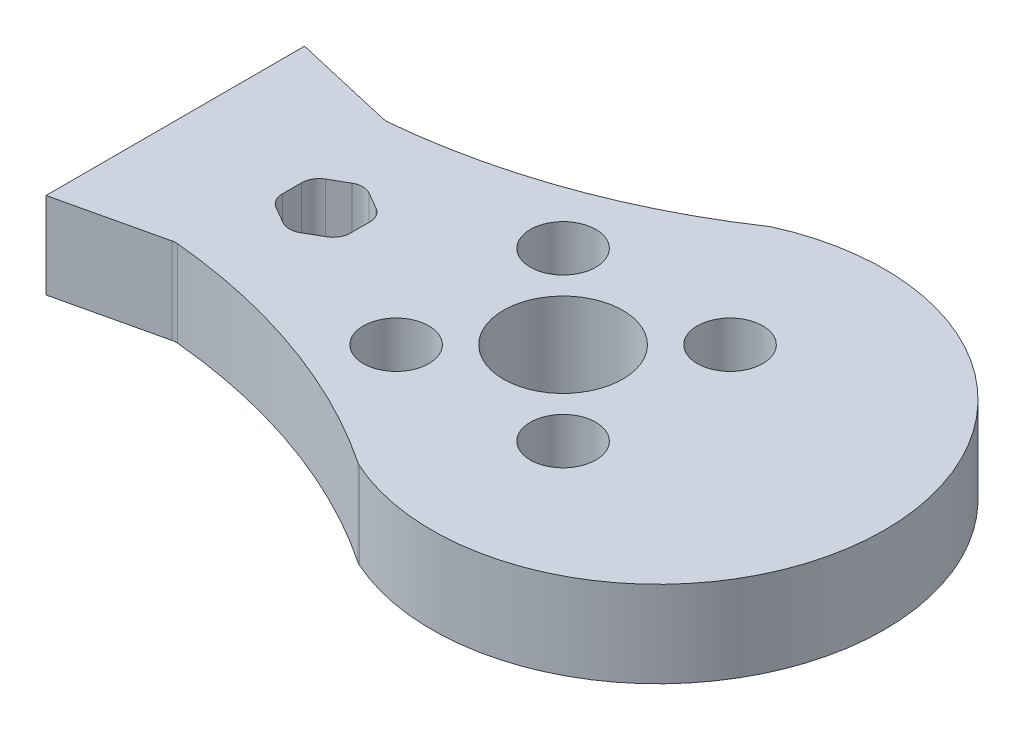
SolidWorks part; units mm, degrees
material "AISI 1020 Steel, Cold Rolled"
ref_plane "Front Plane" through (0, 0, 0) normal (0, 0, 1) x (1, 0, 0)
ref_plane "Top Plane" through (0, 0, 0) normal (0, 1, 0) x (1, 0, 0)
ref_plane "Right Plane" through (0, 0, 0) normal (1, 0, 0) x (0, 0, -1)
other "Center of Mass"
other "Bounding Box"
ref_plane "Default Plane" through (0, 2.286, 19.05) normal (0, -1, 0) x (-1, 0, 0)
sketch "Sketch1" plane through (0, 0, 0) normal (0, 1, 0) x (1, 0, 0)
  line L0 (0, 0) -> (27.8621, 0) construction
  line L1 (-12.303, 12.303) -> (12.303, 12.303) construction
  line L2 (-12.303, 12.303) -> (-12.303, -12.303) construction
  line L3 (-12.303, -12.303) -> (12.303, -12.303) construction
  line L4 (12.303, 12.303) -> (12.303, -12.303) construction
  line L5 (-12.303, 12.303) -> (12.303, -12.303) construction
  line L6 (-12.303, -12.303) -> (12.303, 12.303) construction
  line L7 (-57.15, 19.05) -> (-57.15, -19.05)
  line L8 (-57.15, -19.05) -> (-41.6819, -15.4789)
  line L9 (-39.9415, -2.8963) -> (-34.925, -5.7926)
  line L10 (-34.925, -5.7926) -> (-29.9085, -2.8963)
  line L11 (-29.9085, -2.8963) -> (-29.9085, 2.8963)
  line L12 (-29.9085, 2.8963) -> (-34.925, 5.7926)
  line L13 (-34.925, 5.7926) -> (-39.9415, 2.8963)
  line L14 (-39.9415, 2.8963) -> (-39.9415, -2.8963)
  line L15 (-57.15, 19.05) -> (-41.6819, 15.4789)
  circle A0 centre (0, 0) radius 8.7948
  circle A1 centre (-12.303, 12.303) radius 4.826
  circle A2 centre (12.303, 12.303) radius 4.826
  circle A3 centre (12.303, -12.303) radius 4.826
  circle A4 centre (-12.303, -12.303) radius 4.826
  arc A5 (0.2051, -30.3458) -> (0.2051, 30.3458) centre (14.0081, 0) ccw
  arc A8 (-41.6819, 15.4789) -> (0.2051, 30.3458) centre (-49.53, 104.0318) ccw
  arc A9 (0.2051, -30.3458) -> (-41.6819, -15.4789) centre (-49.53, -104.0318) ccw
  arc A10 (-19.3294, 0) -> (0.2051, -30.3458) centre (14.0081, 0) ccw construction
  circle A11 centre (-34.925, 0) radius 5.0165 construction
  arc A12 (-17.1157, 11.9456) -> (-19.3294, 0) centre (14.0081, 0) ccw construction
  arc A13 (-15.1145, 16.2254) -> (-17.1157, 11.9456) centre (14.0081, 0) ccw construction
  arc A14 (0.2051, 30.3458) -> (-15.1145, 16.2254) centre (14.0081, 0) ccw construction
  arc A15 (-57.15, 15.459) -> (-41.6819, 15.4789) centre (-49.53, 104.0318) ccw construction
  arc A16 (0.2051, 30.3458) -> (-57.15, 15.459) centre (-49.53, 104.0318) ccw construction
  arc A17 (-57.15, -15.459) -> (0.2051, -30.3458) centre (-49.53, -104.0318) ccw construction
  arc A18 (-41.6819, -15.4789) -> (-57.15, -15.459) centre (-49.53, -104.0318) ccw construction
  point P15 (-57.15, 0)
  point P33 (-49.8385, 104.0039)
  point P36 (-50.5698, -101.7291)
  point P37 (-54.0977, -101.4285)
  point P38 (0, 0)
  dimension "D1" = 17.5895
  dimension "D2" = 9.652
  dimension "D4" = 66.675
  dimension "D8" = 77
  dimension "D9" = 10.033
  dimension "D14" = 177.8
  dimension "D3" = 17.399
  dimension "D5" = 38.1
  dimension "D6" = 57.15
  dimension "D7" = 14.0081
  dimension "D10" = 34.925
  dimension "D11" = 47.3456
  dimension "D12" = 77
  dimension "D13" = 15.875
  dimension "D15" = 7.62
extrude "Boss-Extrude1" add sketch "Sketch1" along normal blind 12.7 contours A5 L7 A4 A3 A2 A1 A0 region at (-49.6948, 0, -16.0567)
fillet "Fillet1" radius 2.54 10 edges at (-39.9415, 6.35, 2.8963) (-34.925, 6.35, 5.7926) (-29.9085, 6.35, 2.8963) (-29.9085, 6.35, -2.8963) (-34.925, 6.35, -5.7926) (-39.9415, 6.35, -2.8963) (0.2051, 6.35, -30.3458) (-41.6819, 6.35, -15.4789) (0.2051, 6.35, 30.3458) (-41.6819, 6.35, 15.4789)
equation "\"Unit Measure\"= \"BoundingVolume\" / \"Thickness\"'in^2"
